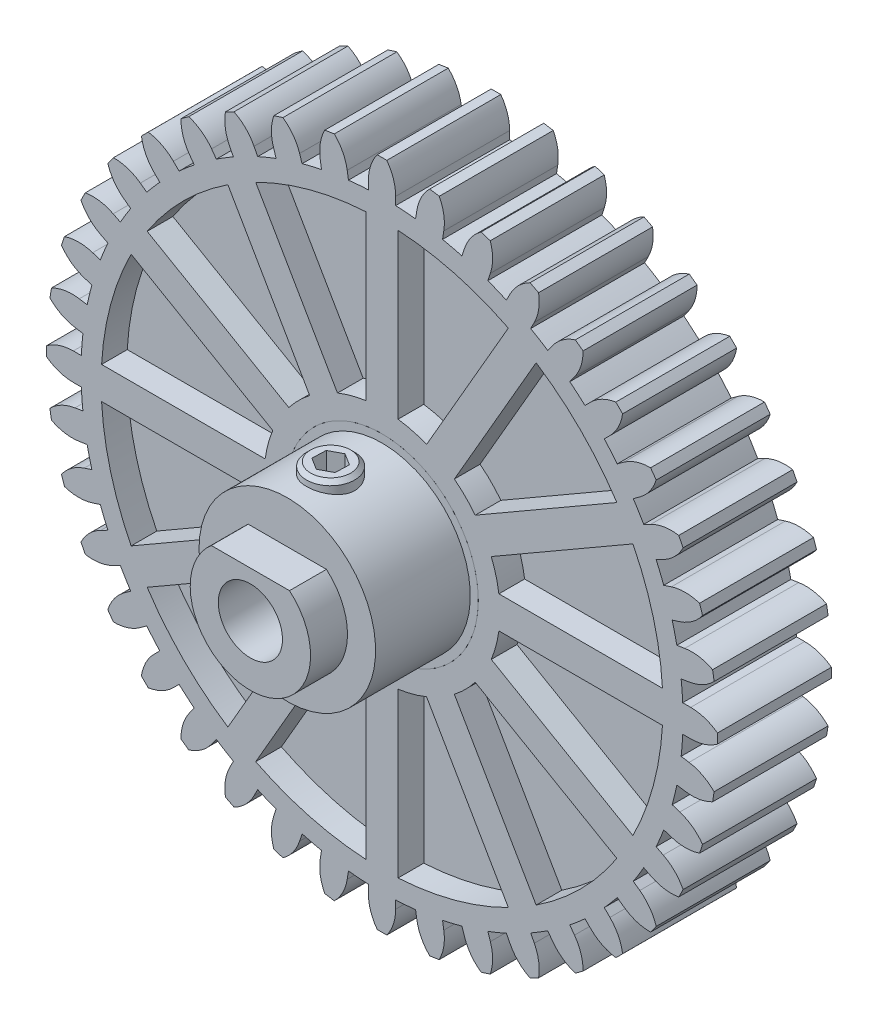
SolidWorks part; units mm, degrees
material "PA Type 6"
material "1060 Alloy"
material "Plain Carbon Steel"
material "PA Type 6"
ref_plane "Front Plane" through (0, 0, 0) normal (0, 0, 1) x (1, 0, 0)
ref_plane "Top Plane" through (0, 0, 0) normal (0, 1, 0) x (1, 0, 0)
ref_plane "Right Plane" through (0, 0, 0) normal (1, 0, 0) x (0, 0, -1)
ref_axis "Axis1" through (0, 0, -11.7513) along (0, 0, 1)
sketch "Sketch4" plane through (0, 0, 0) normal (0, 1, 0) x (1, 0, 0)
  line L0 (0, 23.226) -> (0, -37.2777) construction
  line L1 (2, 0.5) -> (2, -15.3)
  line L2 (2, -15.3) -> (3.75, -15.3)
  line L3 (3.75, -15.3) -> (3.75, -13)
  line L4 (3.75, -13) -> (5.5, -13)
  line L5 (5.5, -13) -> (5.5, -7.1)
  line L6 (5.5, -7.1) -> (6, -7.1)
  line L7 (6, -7.1) -> (6, 0)
  line L8 (6, 0) -> (5.5, 0)
  line L9 (5.5, 0) -> (5.5, 0.5)
  line L10 (5.5, 0.5) -> (2, 0.5)
  dimension "D1" = 4
  dimension "D2" = 11
  dimension "D3" = 12
  dimension "D4" = 7.5
  dimension "D5" = 0.5
  dimension "D6" = 7.1
  dimension "D7" = 15.8
  dimension "D8" = 13.5
revolve "Revolve1" add sketch "Sketch4" angle 360 about L0
sketch "Sketch5" plane through (0, 0, 0) normal (0, 1, 0) x (1, 0, 0)
  line L0 (0, 11.7513) -> (0, -13.6828) construction
  line L1 (-3.75, -15.3) -> (3.75, -15.3) construction
  circle A0 centre (0, -10.3) radius 1.25
  dimension "D2" = 2.5
  dimension "D1" = 5
extrude "Cut-Extrude1" cut sketch "Sketch5" along normal through all
sketch "Sketch6" plane through (0, 0, 13) normal (0, 0, 1) x (1, 0, 0)
  line L1 (2.4372, 4.65) -> (-2.4372, 4.65)
  line L2 (2.4372, 4.65) -> (2.4372, 2.85)
  line L3 (2.4372, 2.85) -> (-2.4372, 2.85)
  line L4 (-2.4372, 4.65) -> (-2.4372, 2.85)
  line L5 (2.4372, 4.65) -> (-2.4372, 2.85) construction
  line L6 (2.4372, 2.85) -> (-2.4372, 4.65) construction
  circle A0 centre (0, 0) radius 3.75 construction
  circle A1 centre (0, 0) radius 3.75 construction
  point P0 (0, 3.75)
  dimension "D1" = 6.6
extrude "Cut-Extrude2" cut sketch "Sketch6" along normal through all
sketch "Sketch1" plane through (0, 0, 0) normal (0, 0, 1) x (1, 0, 0)
  circle A0 centre (0, 0) radius 18.75
  circle A1 centre (0, 0) radius 6
  dimension "D1" = 37.5
  dimension "D2" = 12
extrude "Boss-Extrude1" add sketch "Sketch1" along normal blind 7.1 separate body
sketch "Sketch2" plane through (0, 0, 0) normal (0, 0, 1) x (1, 0, 0)
  line L0 (0, 19.1132) -> (0, -4.5821) construction
  line L1 (0.85, 18.7307) -> (0.85, 19.2307)
  line L2 (-0.85, 18.7307) -> (-0.85, 19.2307)
  line L3 (-0.85, 18.7307) -> (0.85, 18.7307)
  circle A0 centre (0, 0) radius 20.9 construction
  arc A1 (-0.3, 20.8978) -> (0.3, 20.8978) centre (0, 0) cw
  circle A2 centre (0, 0) radius 18.75 construction
  arc A3 (0.85, 19.2307) -> (0.3, 20.8978) centre (-1.9516, 19.2307) ccw
  arc A4 (-0.85, 19.2307) -> (-0.3, 20.8978) centre (1.9516, 19.2307) cw
  dimension "D1" = 41.8
  dimension "D2" = 0.6
  dimension "D3" = 1.7
  dimension "D4" = 0.5
extrude "Boss-Extrude2" add sketch "Sketch2" along normal up to surface (7.1 mm away) contours A3 A1 A4 L2 L3 L1 up to face at (18.75, 0, 7.1)
pattern_circular "CirPattern1" count 40 over 360 about axis through (0, 0, -11.7513) along (0, 0, 1) of "Boss-Extrude2"
sketch "Sketch7" plane through (0, 0, 7.1) normal (0, 0, 1) x (1, 0, 0)
  line L0 (0, 0) -> (0, 31.5134) construction
  line L1 (7.8697, 15.6307) -> (2.7748, 6.8061)
  line L2 (16.1025, 27.8904) -> (0, 0) construction
  line L3 (1, 7.2817) -> (1, 17.4714)
  line L4 (1, 3.7321) -> (1, 31.5134) construction
  line L5 (15.2365, 28.3904) -> (1, 3.7321) construction
  arc A0 (2.7748, 6.8061) -> (1, 7.2817) centre (0, 0) ccw
  arc A1 (7.8697, 15.6307) -> (1, 17.4714) centre (0, 0) ccw
  circle A2 centre (0, 0) radius 7.35 construction
  circle A3 centre (0, 0) radius 17.5 construction
  dimension "D2" = 14.7
  dimension "D3" = 35
  dimension "D1" = 30
  dimension "D4" = 1
extrude "Cut-Extrude3" cut sketch "Sketch7" against normal blind 1.6
sketch "Sketch8" plane through (0, 0, 0) normal (0, 0, -1) x (-1, 0, 0)
  line L2 (-7.8697, 15.6307) -> (-2.7748, 6.8061)
  line L3 (-1, 7.2817) -> (-1, 17.4714)
  line L4 (-7.8697, 15.6307) -> (-2.7748, 6.8061)
  line L5 (-1, 7.2817) -> (-1, 17.4714)
  arc A2 (-1, 7.2817) -> (-2.7748, 6.8061) centre (0, 0) ccw
  arc A3 (-1, 17.4714) -> (-7.8697, 15.6307) centre (0, 0) ccw
  arc A4 (-1, 7.2817) -> (-2.7748, 6.8061) centre (0, 0) ccw
  arc A5 (-1, 17.4714) -> (-7.8697, 15.6307) centre (0, 0) ccw
  dimension "D1" = 0
extrude "Cut-Extrude4" cut sketch "Sketch8" against normal blind 1.6
pattern_circular "CirPattern2" count 12 over 360 about axis through (0, 0, -11.7513) along (0, 0, 1) of "Cut-Extrude4", "Cut-Extrude3"
ref_plane "Plane1" through (0, 1.5, 0) normal (0, 1, 0) x (1, 0, 0)
sketch "Sketch9" plane through (0, 1.5, 0) normal (0, 1, 0) x (1, 0, 0)
  circle A0 centre (0, -10.3) radius 1.5
  dimension "D1" = 3
extrude "Boss-Extrude3" add sketch "Sketch9" along normal blind 4.6 separate body
chamfer "Chamfer1" distance 0.25 angle 45 1 edges at (0, 6.1, 11.8)
sketch "Sketch10" plane through (0, 6.1, 0) normal (0, 1, 0) x (1, 0, 0)
  line L1 (0.7336, -10.7603) -> (0.7654, -9.8948)
  line L2 (0.7654, -9.8948) -> (0.0318, -9.4346)
  line L3 (0.0318, -9.4346) -> (-0.7336, -9.8397)
  line L4 (-0.7336, -9.8397) -> (-0.7654, -10.7052)
  line L5 (-0.7654, -10.7052) -> (-0.0318, -11.1654)
  line L6 (-0.0318, -11.1654) -> (0.7336, -10.7603)
  circle A0 centre (0, -10.3) radius 0.75 construction
  dimension "D1" = 1.5
extrude "Cut-Extrude5" cut sketch "Sketch10" against normal blind 2
